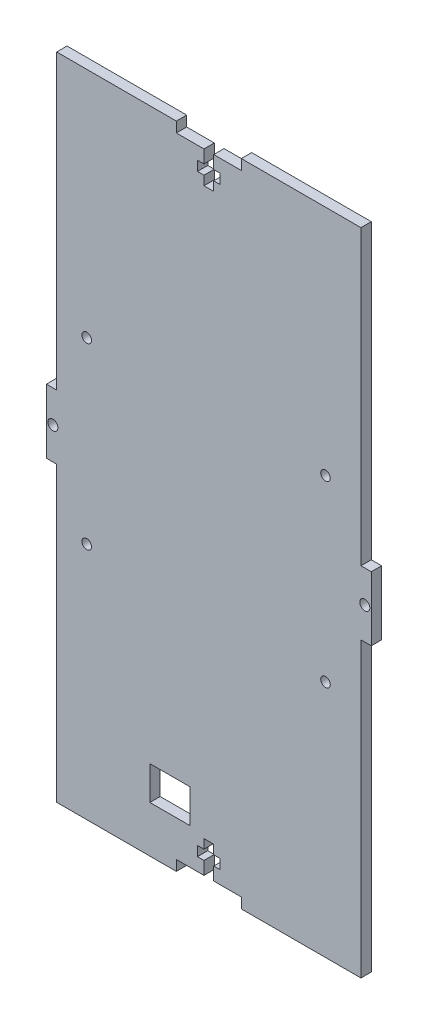
SolidWorks part; units mm, degrees
ref_plane "Front Plane" through (0, 0, 0) normal (0, 0, 1) x (1, 0, 0)
ref_plane "Top Plane" through (0, 0, 0) normal (0, 1, 0) x (1, 0, 0)
ref_plane "Right Plane" through (0, 0, 0) normal (1, 0, 0) x (0, 0, -1)
sketch "Sketch1" plane through (0, 0, 0) normal (0, 0, 1) x (1, 0, 0)
  line L0 (0, 40) -> (0, -40) construction
  line L5 (-50, -100) -> (50, 100) construction
  line L6 (-50, 100) -> (50, -100) construction
  line L7 (-100, 0) -> (100, 0) construction
  line L32 (-50, 100) -> (50, 100)
  line L35 (50, 100) -> (50, -100)
  line L36 (50, -100) -> (-50, -100)
  line L37 (-50, -100) -> (-50, 100)
  point P0 (0, 0)
  dimension "D1" = 100
  dimension "D2" = 200
extrude "Boss-Extrude2" add sketch "Sketch1" along normal blind 3.18
sketch "Sketch2" plane through (0, 0, 3.18) normal (0, 0, 1) x (1, 0, 0)
  line L0 (0, -100) -> (0, 100) construction
  line L1 (-123.0225, 0) -> (147.0753, 0) construction
  line L2 (50, 100) -> (-50, 100) construction
  line L4 (-10, 100) -> (-10, 96.82)
  line L5 (-10, 96.82) -> (-1.5, 96.82)
  line L6 (10, 100) -> (10, 96.82)
  line L7 (1.5, 96.82) -> (10, 96.82)
  line L9 (-1.5, 96.82) -> (-1.5, 92.82)
  line L10 (-1.5, 87) -> (1.5, 87)
  line L11 (1.5, 96.82) -> (1.5, 92.82)
  line L12 (-3.5, 92.82) -> (-1.5, 92.82)
  line L13 (-3.5, 92.82) -> (-3.5, 89.82)
  line L14 (-3.5, 89.82) -> (-1.5, 89.82)
  line L15 (3.5, 92.82) -> (3.5, 89.82)
  line L16 (1.5, 92.82) -> (3.5, 92.82)
  line L17 (-1.5, 89.82) -> (-1.5, 87)
  line L18 (1.5, 89.82) -> (1.5, 87)
  line L19 (1.5, 89.82) -> (3.5, 89.82)
  line L20 (-10, 100) -> (10, 100)
  line L21 (-50, -100) -> (50, -100) construction
  line L22 (-50, 100) -> (-50, -100) construction
  line L23 (-50, 9.875) -> (-46.82, 9.875)
  line L24 (-50, 9.875) -> (-50, 100)
  line L25 (-50, 100) -> (-46.82, 100)
  line L26 (-46.82, 9.875) -> (-46.82, 100)
  line L28 (-50, -9.875) -> (-46.82, -9.875)
  line L29 (-50, -9.875) -> (-50, -100)
  line L30 (-50, -100) -> (-46.82, -100)
  line L31 (-46.82, -9.875) -> (-46.82, -100)
  circle A0 centre (-48, 0) radius 1.55
  dimension "D11" = 3.1
  dimension "D12" = 2
  dimension "D1" = 4
  dimension "D2" = 3
  dimension "D3" = 3
  dimension "D4" = 20
  dimension "D5" = 7
  dimension "D6" = 3.18
  dimension "D7" = 13
  dimension "D8" = 19.75
  dimension "D9" = 3.18
  dimension "D10" = 3.18
extrude "Cut-Extrude1" cut sketch "Sketch2" against normal through all
mirror "Mirror1" about plane through (0, 0, 0) normal (0, 1, 0) of "Cut-Extrude1"
mirror "Mirror3" about plane through (0, 0, 0) normal (1, 0, 0) of "Cut-Extrude1"
sketch "Sketch4" plane through (0, 0, 3.18) normal (0, 0, 1) x (1, 0, 0)
  line L5 (-18.15, -85.7) -> (-5.7964, -85.7)
  line L6 (-18.15, -85.7) -> (-18.15, -75.3464)
  line L7 (-18.15, -75.3464) -> (-5.7964, -75.3464)
  line L8 (-5.7964, -85.7) -> (-5.7964, -75.3464)
  arc A0 (-5.65, -75.7) -> (-6.15, -75.2) centre (-6.15, -75.7) ccw construction
extrude "Cut-Extrude3" cut sketch "Sketch4" against normal through all
sketch "Sketch5" plane through (0, 0, 3.18) normal (0, 0, 1) x (1, 0, 0)
  circle A0 centre (-37.5809, 28.4641) radius 1.47
  circle A1 centre (35.9045, 28.4641) radius 1.47
  circle A2 centre (-37.5809, -26.5359) radius 1.47
  circle A3 centre (35.9045, -26.5359) radius 1.47
  circle A4 centre (-37.5809, 28.4641) radius 1.47 construction
  circle A5 centre (35.9045, 28.4641) radius 1.47 construction
  circle A6 centre (35.9045, -26.5359) radius 1.47 construction
  circle A8 centre (-37.5809, -26.5359) radius 1.47 construction
  point P14 (0, 0)
extrude "Cut-Extrude4" cut sketch "Sketch5" against normal through all
